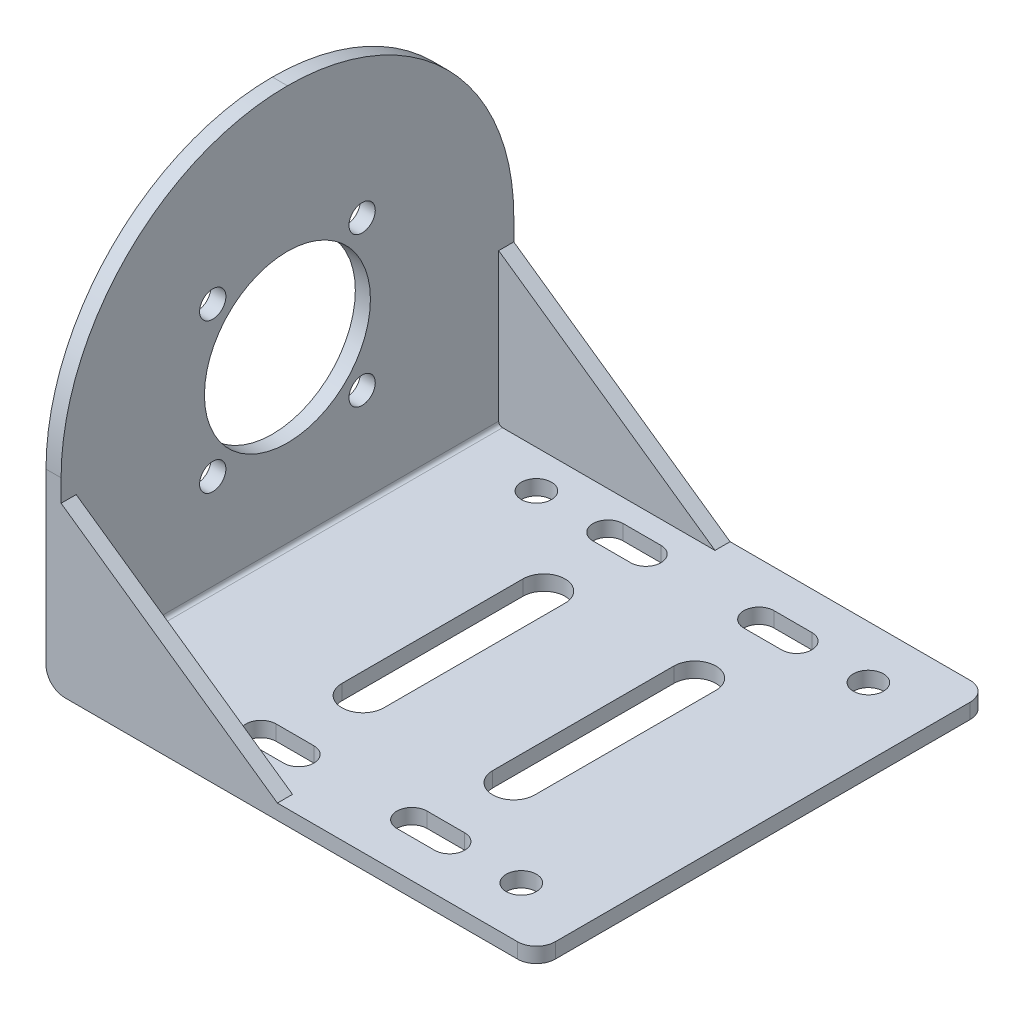
SolidWorks part; units mm, degrees
ref_plane "Front Plane" through (0, 0, 0) normal (0, 0, 1) x (1, 0, 0)
ref_plane "Top Plane" through (0, 0, 0) normal (0, 1, 0) x (1, 0, 0)
ref_plane "Right Plane" through (0, 0, 0) normal (1, 0, 0) x (0, 0, -1)
sketch "Sketch2" plane through (0, 0, 0) normal (0, 0, 1) x (1, 0, 0)
  line L0 (0.5, 0) -> (63, 0)
  line L1 (63, 0) -> (63, -2)
  line L2 (63, -2) -> (0.5, -2)
  line L3 (-2, 0.5) -> (-2, 53)
  line L4 (-2, 53) -> (0, 53)
  line L5 (0, 53) -> (0, 0.5)
  arc A0 (-2, 0.5) -> (0.5, -2) centre (0.5, 0.5) ccw
  arc A1 (0, 0.5) -> (0.5, 0) centre (0.5, 0.5) ccw
  point P3 (0.5, 0.5)
  dimension "D3" = 2
  dimension "D4" = 2
  dimension "D5" = 2.5
  dimension "D6" = 2.5
extrude "Boss-Extrude1" add sketch "Sketch2" along normal blind 60
fillet "Fillet2" radius 2.5 1 edges at (63, -1, 60) type face fillet first side face at (15.2973, 12.7973, 60) second side face at (63, -1, 30)
fillet "Fillet3" radius 2.5 1 edges at (63, -1, 0) type face fillet first side face at (63, -1, 28.75) second side face at (15.2973, 12.7973, 0)
fillet "Fillet4" radius 30 1 edges at (-1, 53, 60) type face fillet first side face at (-1, 53, 30) second side face at (14.6723, 12.7973, 60)
fillet "Fillet5" radius 30 1 edges at (-1, 53, 0) type face fillet first side face at (14.6723, 12.7973, 0) second side face at (-1, 53, 15)
sketch "Sketch3" plane through (0, 0, 0) normal (1, 0, 0) x (0, 0, -1)
  line L0 (-30, 23) -> (-30, 9.3528) construction
  line L1 (-39.8995, 13.1005) -> (-30, 23) construction
  circle A0 centre (-30, 23) radius 11
  arc A1 (0, 23) -> (-30, 53) centre (-30, 23) ccw construction
  circle A2 centre (-39.8995, 13.1005) radius 1.7424
  circle A3 centre (-39.8995, 32.8995) radius 1.7424
  circle A4 centre (-20.1005, 32.8995) radius 1.7424
  circle A5 centre (-20.1005, 13.1005) radius 1.7424
  point P16 (-30, 23)
  dimension "D1" = 14
  dimension "D3" = 45
  dimension "D2" = 4
extrude "Cut-Extrude1" cut sketch "Sketch3" against normal blind 5
sketch "Sketch4" plane through (0, 0, 60) normal (0, 0, 1) x (1, 0, 0)
  line L0 (0, 20.0752) -> (28.6703, 0)
  line L1 (0, 0.5) -> (0, 23) construction
  line L2 (60.5, 0) -> (0.5, 0) construction
  line L3 (28.6703, 0) -> (0.5, 0)
  line L4 (0, 0.5) -> (0, 20.0752)
  arc A0 (0.5, 0) -> (0, 0.5) centre (0.5, 0.5) cw
  arc A2 (0, 0.5) -> (0.5, 0) centre (0.5, 0.5) ccw construction
  dimension "D1" = 55
  dimension "D2" = 35
extrude "Boss-Extrude3" add sketch "Sketch4" against normal blind 2
sketch "Sketch6" plane through (0, 0, 0) normal (0, 0, -1) x (-1, 0, 0)
  line L0 (0, 20.0752) -> (-28.6703, 0)
  line L1 (-28.6703, 0) -> (-0.5, 0)
  line L2 (0, 0.5) -> (0, 20.0752)
  line L3 (0, 53) -> (0, 0.5) construction
  line L4 (-28.6703, 0) -> (0, 20.0752) construction
  arc A1 (-0.5, 0) -> (0, 0.5) centre (-0.5, 0.5) ccw
  arc A2 (-0.5, 0) -> (0, 0.5) centre (-0.5, 0.5) ccw construction
  line M7 (0, 23) -> (0, 0.5)
  arc M8 (0, 0.5) -> (-0.5, 0) centre (-0.5, 0.5) cw
  line M9 (-0.5, 0) -> (-60.5, 0)
extrude "Boss-Extrude4" add sketch "Sketch6" against normal blind 2 contours L0 M7 M9 M8 region at (9.5585, 6.693, 0)
sketch "Sketch7" plane through (0, 0, 0) normal (0, 1, 0) x (1, 0, 0)
  line L0 (22, -18) -> (22, -42) construction
  line L1 (0, 0) -> (28.6703, 0) construction
  line L2 (60.5, 0) -> (28.6703, 0) construction
  line L3 (44.5, -53) -> (39.5, -53) construction
  line L4 (44.5, -55) -> (39.5, -55)
  line L5 (44.5, -51) -> (39.5, -51)
  line L6 (44.5, -7) -> (39.5, -7) construction
  line L7 (44.5, -9) -> (39.5, -9)
  line L8 (44.5, -5) -> (39.5, -5)
  line L9 (24.5, -7) -> (19.5, -7) construction
  line L10 (24.5, -9) -> (19.5, -9)
  line L11 (24.5, -5) -> (19.5, -5)
  line L12 (24.5, -53) -> (19.5, -53) construction
  line L13 (24.5, -55) -> (19.5, -55)
  line L14 (24.5, -51) -> (19.5, -51)
  line L15 (24.7911, -18) -> (24.7911, -42)
  line L16 (19.2089, -18) -> (19.2089, -42)
  line L17 (42, -18) -> (42, -42) construction
  line L18 (44.7911, -18) -> (44.7911, -42)
  line L19 (39.2089, -18) -> (39.2089, -42)
  circle A0 centre (54, -53) radius 2
  circle A1 centre (54, -7) radius 2
  arc A2 (44.5, -55) -> (44.5, -51) centre (44.5, -53) ccw
  arc A3 (39.5, -51) -> (39.5, -55) centre (39.5, -53) ccw
  arc A4 (44.5, -9) -> (44.5, -5) centre (44.5, -7) ccw
  arc A5 (39.5, -5) -> (39.5, -9) centre (39.5, -7) ccw
  arc A6 (24.5, -9) -> (24.5, -5) centre (24.5, -7) ccw
  arc A7 (19.5, -5) -> (19.5, -9) centre (19.5, -7) ccw
  arc A8 (24.5, -55) -> (24.5, -51) centre (24.5, -53) ccw
  arc A9 (19.5, -51) -> (19.5, -55) centre (19.5, -53) ccw
  circle A10 centre (10, -7) radius 2
  circle A11 centre (10, -53) radius 2
  arc A12 (24.7911, -18) -> (19.2089, -18) centre (22, -18) ccw
  arc A13 (19.2089, -42) -> (24.7911, -42) centre (22, -42) ccw
  arc A14 (44.7911, -18) -> (39.2089, -18) centre (42, -18) ccw
  arc A15 (39.2089, -42) -> (44.7911, -42) centre (42, -42) ccw
  point P8 (42, -53)
  point P17 (42, -7)
  point P25 (22, -7)
  point P32 (22, -30)
  point P37 (22, -53)
  point P50 (42, -30)
  dimension "D2" = 12
  dimension "D3" = 7
  dimension "D4" = 5
  dimension "D5" = 4
  dimension "D6" = 12
  dimension "D7" = 4
  dimension "D8" = 5
  dimension "D9" = 4
  dimension "D10" = 20
  dimension "D11" = 5
  dimension "D12" = 12
  dimension "D13" = 4
  dimension "D14" = 20
  dimension "D15" = 5
  dimension "D16" = 12
  dimension "D17" = 30
  dimension "D18" = 24
  dimension "D19" = 24
extrude "Cut-Extrude2" cut sketch "Sketch7" against normal blind 2
